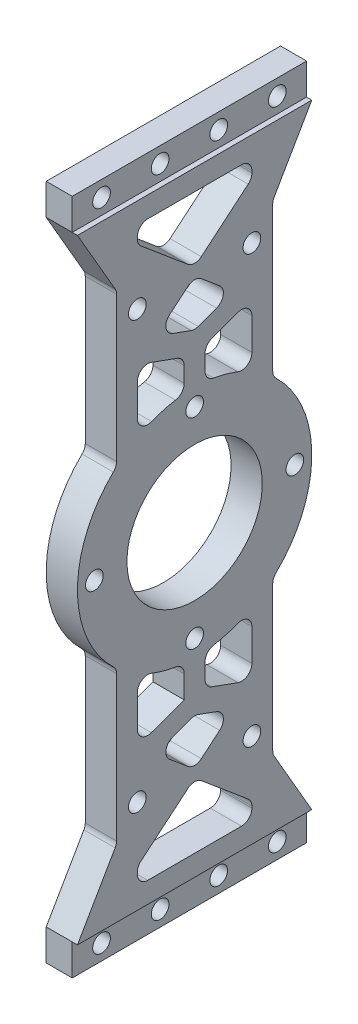
SolidWorks part; units mm, degrees
material "Сплав 2024"
ref_plane "Спереди" through (0, 0, 0) normal (0, 0, 1) x (1, 0, 0)
ref_plane "Сверху" through (0, 0, 0) normal (0, 1, 0) x (1, 0, 0)
ref_plane "Справа" through (0, 0, 0) normal (1, 0, 0) x (0, 0, -1)
sketch "Эскиз1" plane through (0, 0, 0) normal (0, 1, 0) x (1, 0, 0)
  line L1 (0, 0) -> (6, 0)
  line L2 (0, 0) -> (0, -30)
  line L3 (0, -30) -> (6, -30)
  line L4 (6, 0) -> (6, -30)
  dimension "D1" = 6
  dimension "D2" = 30
extrude "Бобышка-Вытянуть1" add sketch "Эскиз1" along normal blind 130
sketch "Эскиз2" plane through (0, 0, 0) normal (-1, 0, 0) x (0, 0, 1)
  line L0 (30, 65) -> (0, 65) construction
  line L1 (30, 130) -> (30, 0) construction
  line L2 (0, 130) -> (0, 0) construction
  line L3 (15, 130) -> (15, 0) construction
  line L4 (0, 130) -> (30, 130) construction
  line L5 (0, 0) -> (30, 0) construction
  circle A0 centre (15, 65) radius 22.5
  dimension "D1" = 45
extrude "Бобышка-Вытянуть2" add sketch "Эскиз2" against normal up to surface (6 mm away) up to face at (6, 65, 15)
sketch "Эскиз3" plane through (0, 0, 0) normal (-1, 0, 0) x (0, 0, 1)
  circle A0 centre (15, 65) radius 13
  dimension "D1" = 26
extrude "Вырез-Вытянуть1" cut sketch "Эскиз3" against normal through all
sketch "Эскиз4" plane through (6, 0, 0) normal (-1, 0, 0) x (0, 0, 1)
  line L0 (15, 87.5) -> (15, 42.5) construction
  line L1 (15, 130) -> (15, 0) construction
  line L2 (37.5, 65) -> (-7.5, 65) construction
  circle A0 centre (15, 65) radius 19.25 construction
  circle A1 centre (15, 65) radius 22.5 construction
  dimension "D1" = 38.5
hole_wizard "Отверстие с зазором M33" positions "Эскиз6" profile "Эскиз5" hole size "M3" standard "Ansi Metric" end condition through all
sketch "Эскиз6" plane through (6, -25.0247, 7.2629) normal (-1, 0, 0) x (0, 0, 1)
  line L0 (7.7371, 112.5247) -> (7.7371, 67.5247) construction
  line L1 (30.2371, 90.0247) -> (-14.7629, 90.0247) construction
  circle A0 centre (7.7371, 90.0247) radius 19.25 construction
  point P0 (7.7371, 109.2747)
  point P6 (-11.5129, 90.0247)
  point P10 (7.7371, 70.7747)
  point P12 (26.9871, 90.0247)
sketch "Эскиз5" plane through (6, 84.25, 15) normal (0, 1, 0) x (0, 0, -1)
  line L0 (0, 0) -> (0, 6)
  line L1 (0, 6) -> (1.7, 6)
  line L2 (1.7, 6) -> (1.7, 0)
  line L5 (1.7, 0) -> (0, 0)
  line L11 (0, -6.35) -> (0, 107.95) construction
  dimension "Диаметр сквозного отверстия" = 3.4
  dimension "Глубина сквозного отверстия" = 6
sketch "Эскиз8" plane through (6, 0, 0) normal (1, 0, 0) x (0, 0, -1)
  line L0 (-15, 130) -> (-15, 0) construction
  line L1 (-30, 130) -> (0, 130) construction
  line L2 (-30, 0) -> (0, 0) construction
  line L3 (19.447, 65) -> (-49.447, 65) construction
  line L4 (0, 130) -> (0, 81.7705) construction
  line L5 (-26, 106) -> (-4, 106) construction
  line L6 (-26, 106) -> (-26, 24) construction
  line L7 (-26, 24) -> (-4, 24) construction
  line L8 (-4, 106) -> (-4, 24) construction
  line L9 (-26, 106) -> (-4, 24) construction
  line L10 (-26, 24) -> (-4, 106) construction
  point P8 (-15, 65)
  point P9 (-15, 65)
  dimension "D1" = 4
  dimension "D2" = 82
hole_wizard "Отверстие с зазором M32" positions "Эскиз10" profile "Эскиз9" hole size "M3" standard "Ansi Metric" end condition through all
sketch "Эскиз10" plane through (6, 0, 0) normal (1, 0, 0) x (0, 0, -1)
  point P0 (-26, 106)
  point P3 (-4, 106)
  point P6 (-4, 24)
  point P9 (-26, 24)
sketch "Эскиз9" plane through (6, 106, 26) normal (0, 1, 0) x (0, 0, -1)
  line L0 (0, 0) -> (0, 6)
  line L1 (0, 6) -> (1.7, 6)
  line L2 (1.7, 6) -> (1.7, 0)
  line L5 (1.7, 0) -> (0, 0)
  line L11 (0, -6.35) -> (0, 107.95) construction
  dimension "Диаметр сквозного отверстия" = 3.4
  dimension "Глубина сквозного отверстия" = 6
sketch "Эскиз11" plane through (6, 0, 0) normal (1, 0, 0) x (0, 0, -1)
  line L0 (-15, 130) -> (-15, 0) construction
  line L1 (-30, 130) -> (0, 130) construction
  line L2 (-30, 0) -> (0, 0) construction
  line L3 (-37.5, 124) -> (-30, 111.0096)
  line L4 (-37.5, 124) -> (7.5, 124) construction
  line L5 (-37.5, 124) -> (-37.5, 130)
  line L6 (-37.5, 130) -> (7.5, 130)
  line L7 (7.5, 124) -> (7.5, 130)
  line L8 (-37.5, 124) -> (7.5, 130) construction
  line L9 (-37.5, 130) -> (7.5, 124) construction
  line L10 (-30, 130) -> (-30, 81.7705) construction
  line L11 (-30, 111.0096) -> (0, 111.0096)
  line L12 (0, 130) -> (0, 81.7705) construction
  line L13 (0, 111.0096) -> (7.5, 124)
  line L14 (-37.5, 127) -> (7.5, 127) construction
  line L15 (-31.875, 130) -> (-31.875, 124) construction
  line L16 (-26.25, 130) -> (-26.25, 124) construction
  line L17 (-20.625, 130) -> (-20.625, 124) construction
  line L18 (-15, 130) -> (-15, 124) construction
  line L19 (-15, 65) -> (-5.455, 65) construction
  line L20 (-15, 0) -> (-15, 6) construction
  line L21 (-20.625, 0) -> (-20.625, 6) construction
  line L22 (-26.25, 0) -> (-26.25, 6) construction
  line L23 (-31.875, 0) -> (-31.875, 6) construction
  line L24 (-37.5, 3) -> (7.5, 3) construction
  line L25 (-37.5, 0) -> (7.5, 6) construction
  line L26 (-37.5, 6) -> (7.5, 0) construction
  line L27 (-37.5, 6) -> (7.5, 6) construction
  line L28 (0, 18.9904) -> (7.5, 6)
  line L29 (-30, 18.9904) -> (0, 18.9904)
  line L30 (7.5, 6) -> (7.5, 0)
  line L31 (-37.5, 0) -> (7.5, 0)
  line L32 (-37.5, 6) -> (-37.5, 0)
  line L33 (-37.5, 6) -> (-30, 18.9904)
  line L34 (-9.375, 130) -> (-9.375, 124) construction
  line L35 (-3.75, 130) -> (-3.75, 124) construction
  line L36 (1.875, 130) -> (1.875, 124) construction
  line L37 (-9.375, 0) -> (-9.375, 6) construction
  line L38 (-3.75, 0) -> (-3.75, 6) construction
  line L39 (1.875, 0) -> (1.875, 6) construction
  point P6 (-15, 127)
  point P45 (-15, 3)
  dimension "D1" = 6
  dimension "D2" = 45
  dimension "D3" = 120
  dimension "D4" = 5.625
  dimension "D5" = 5.625
  dimension "D6" = 5.625
  dimension "D7" = 5.625
  dimension "D8" = 5.625
  dimension "D9" = 5.625
  dimension "D10" = 5.625
extrude "Бобышка-Вытянуть3" add sketch "Эскиз11" against normal up to surface (6 mm away) up to face at (0, 106, 24.3)
hole_wizard "Отверстие с зазором M31" positions "Эскиз13" profile "Эскиз12" hole size "M3" standard "Ansi Metric" end condition through all
sketch "Эскиз13" plane through (6, 0, 0) normal (1, 0, 0) x (0, 0, -1)
  line L0 (-31.875, 130) -> (-31.875, 124) construction
  line L4 (-31.875, 0) -> (-31.875, 6) construction
  line L8 (1.875, 130) -> (1.875, 124) construction
  line L9 (-9.375, 130) -> (-9.375, 124) construction
  line L10 (-20.625, 130) -> (-20.625, 124) construction
  line L11 (1.875, 0) -> (1.875, 6) construction
  line L12 (-9.375, 0) -> (-9.375, 6) construction
  line L13 (-20.625, 0) -> (-20.625, 6) construction
  point P0 (-31.875, 127)
  point P4 (-20.625, 127)
  point P8 (-9.375, 127)
  point P12 (1.875, 127)
  point P16 (-31.875, 3)
  point P20 (-20.625, 3)
  point P24 (-9.375, 3)
  point P28 (1.875, 3)
sketch "Эскиз12" plane through (6, 127, 31.875) normal (0, 1, 0) x (0, 0, -1)
  line L0 (0, 0) -> (0, 6)
  line L1 (0, 6) -> (1.7, 6)
  line L2 (1.7, 6) -> (1.7, 0)
  line L5 (1.7, 0) -> (0, 0)
  line L11 (0, -6.35) -> (0, 107.95) construction
  dimension "Диаметр сквозного отверстия" = 3.4
  dimension "Глубина сквозного отверстия" = 6
sketch "Эскиз14" plane through (6, 0, 0) normal (1, 0, 0) x (0, 0, -1)
  line L1 (-37.5, 130) -> (7.5, 130)
  line L2 (-37.5, 130) -> (-37.5, 124)
  line L3 (-37.5, 124) -> (7.5, 124)
  line L4 (7.5, 130) -> (7.5, 124)
  line L5 (-37.5, 0) -> (7.5, 0)
  line L6 (-37.5, 0) -> (-37.5, 6)
  line L7 (-37.5, 6) -> (7.5, 6)
  line L8 (7.5, 0) -> (7.5, 6)
extrude "Вырез-Вытянуть2" cut sketch "Эскиз14" against normal blind 1
sketch "Эскиз15" plane through (6, 0, 0) normal (1, 0, 0) x (0, 0, -1)
  line L0 (-26, 0) -> (-26, 130) construction
  line L1 (-37.5, 0) -> (7.5, 0) construction
  line L2 (7.5, 130) -> (-37.5, 130) construction
  line L3 (-4, 130) -> (-4, 0) construction
  line L4 (-30, 48.2295) -> (-30, 18.9904) construction
  line L5 (0, 48.2295) -> (0, 18.9904) construction
  line L6 (-15, 65) -> (0, 65) construction
  line L7 (-17, 42.5891) -> (-17, 36.5058)
  line L8 (-13, 42.5891) -> (-13, 36.5058)
  line L9 (-15, 130) -> (-15, 0) construction
  line L10 (-26, 24) -> (-4, 24) construction
  line L11 (-17, 36.5058) -> (-26, 33.2301)
  line L12 (-26, 33.2301) -> (-26, 45.3722)
  line L13 (-13, 36.5058) -> (-4, 33.2301)
  line L14 (-4, 33.2301) -> (-4, 45.3722)
  line L15 (-15, 32.9771) -> (-22.4618, 30.2612)
  line L16 (-22.4618, 30.2612) -> (-15, 24)
  line L17 (-15, 24) -> (-7.5382, 30.2612)
  line L18 (-7.5382, 30.2612) -> (-15, 32.9771)
  line L19 (-26, 33.2301) -> (-15, 24) construction
  line L20 (-4, 33.2301) -> (-15, 24) construction
  line L21 (-30, 22.5) -> (0, 22.5) construction
  line L22 (-15, 22.5) -> (-26, 13.2699) construction
  line L23 (-15, 22.5) -> (-4, 13.2699) construction
  line L24 (-4, 13.2699) -> (-26, 13.2699) construction
  line L25 (-15, 22.5) -> (-26, 13.2699)
  line L26 (-35.1906, 10) -> (5.1906, 10) construction
  line L27 (-30, 18.9904) -> (-37.5, 6) construction
  line L28 (7.5, 6) -> (0, 18.9904) construction
  line L29 (7.5, 6) -> (-37.5, 6) construction
  line L30 (-26, 13.2699) -> (-26, 10)
  line L31 (-26, 10) -> (-4, 10)
  line L32 (-4, 10) -> (-4, 13.2699)
  line L33 (-4, 13.2699) -> (-15, 22.5)
  line L34 (-13, 87.4109) -> (-13, 93.4942)
  line L35 (-13, 93.4942) -> (-4, 96.7699)
  line L36 (-4, 96.7699) -> (-4, 84.6278)
  line L37 (-26, 96.7699) -> (-26, 84.6278)
  line L38 (-17, 93.4942) -> (-26, 96.7699)
  line L39 (-17, 87.4109) -> (-17, 93.4942)
  line L40 (-7.5382, 99.7388) -> (-15, 97.0229)
  line L41 (-15, 97.0229) -> (-22.4618, 99.7388)
  line L42 (-22.4618, 99.7388) -> (-15, 106)
  line L43 (-15, 106) -> (-7.5382, 99.7388)
  line L44 (-4, 120) -> (-4, 116.7301)
  line L45 (-4, 116.7301) -> (-15, 107.5)
  line L46 (-15, 107.5) -> (-26, 116.7301)
  line L47 (-26, 116.7301) -> (-26, 120)
  line L48 (-26, 120) -> (-4, 120)
  circle A0 centre (-15, 65) radius 22.5 construction
  arc A1 (-26, 45.3722) -> (-17, 42.5891) centre (-15, 65) ccw
  arc A2 (-13, 42.5891) -> (-4, 45.3722) centre (-15, 65) ccw
  arc A3 (-13, 87.4109) -> (-4, 84.6278) centre (-15, 65) cw
  arc A4 (-26, 84.6278) -> (-17, 87.4109) centre (-15, 65) cw
  point P22 (-26, 45.3722)
  point P23 (-4, 45.3722)
  point P40 (-15, 22.5)
  dimension "D5" = 110
  dimension "D1" = 4
  dimension "D2" = 4
  dimension "D3" = 4
  dimension "D4" = 2
  dimension "D6" = 100
  dimension "D7" = 4
  dimension "D8" = 1.5
  dimension "D9" = 4
  dimension "D10" = 100
extrude "Вырез-Вытянуть3" cut sketch "Эскиз15" against normal up to next
fillet "Скругление1" radius 2 8 edges at (3, 111.0096, 0) (3, 81.7705, 0) (3, 48.2295, 0) (3, 18.9904, 0) (3, 18.9904, 30) (3, 48.2295, 30) (3, 81.7705, 30) (3, 111.0096, 30)
fillet "Скругление2" radius 2 33 edges at (3, 13.2699, 4) (3, 10, 4) (3, 13.2699, 26) (3, 10, 26) (3, 24, 15) (3, 33.2301, 4) (3, 30.2612, 7.5382) (3, 30.2612, 22.4618) (3, 36.5058, 13) (3, 33.2301, 26) (3, 45.3722, 4) (3, 42.5891, 17) (3, 22.5, 15) (3, 32.9771, 15) (3, 45.3722, 26) (3, 42.5891, 13) (3, 84.6278, 26) (3, 96.7699, 26) (3, 87.4109, 13) (3, 93.4942, 13) (3, 84.6278, 4) (3, 96.7699, 4) (3, 93.4942, 17) (3, 87.4109, 17) (3, 99.7388, 7.5382) (3, 97.0229, 15) (3, 99.7388, 22.4618) (3, 106, 15) (3, 120, 4) (3, 116.7301, 4) (3, 107.5, 15) (3, 116.7301, 26) (3, 120, 26)
equation "\"D4@Эскиз11\"=\"D2@Эскиз11\"/8"
equation "\"D5@Эскиз11\"=\"D4@Эскиз11\""
equation "\"D6@Эскиз11\"=\"D4@Эскиз11\""
equation "\"D7@Эскиз11\"=\"D4@Эскиз11\""
equation "\"D8@Эскиз11\"=\"D4@Эскиз11\""
equation "\"D9@Эскиз11\"=\"D4@Эскиз11\""
equation "\"D10@Эскиз11\"=\"D4@Эскиз11\""
